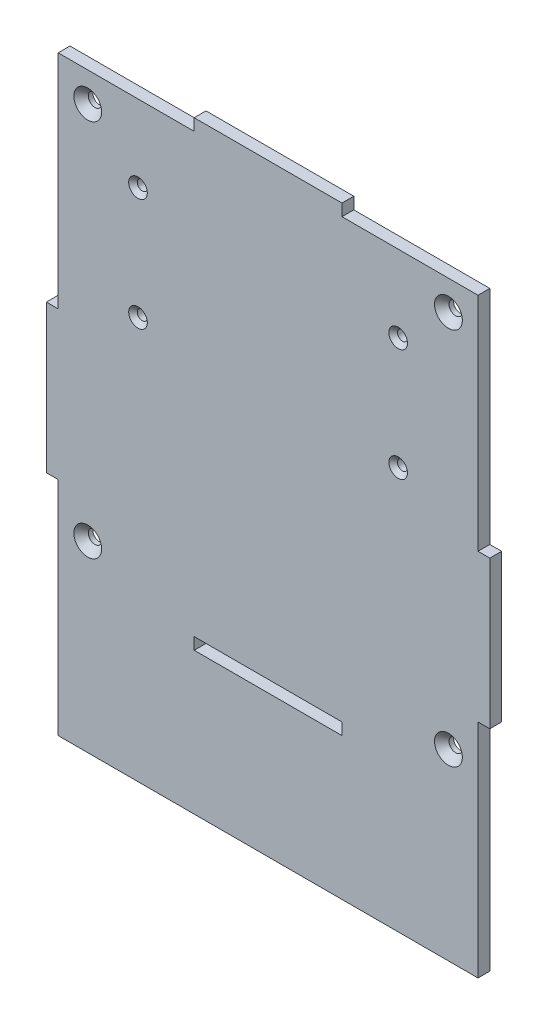
SolidWorks part; units mm, degrees
ref_plane "Front Plane" through (0, 0, 0) normal (0, 0, 1) x (1, 0, 0)
ref_plane "Top Plane" through (0, 0, 0) normal (0, 1, 0) x (1, 0, 0)
ref_plane "Right Plane" through (0, 0, 0) normal (1, 0, 0) x (0, 0, -1)
sketch "Sketch1" plane through (0, 0, 0) normal (0, 0, 1) x (1, 0, 0)
  line L0 (0, 104) -> (0, 0) construction
  line L1 (-71, -100) -> (71, -100)
  line L2 (-71, -100) -> (-71, 100)
  line L3 (-71, 100) -> (71, 100)
  line L4 (71, -100) -> (71, 100)
  line L5 (-71, -100) -> (71, 100) construction
  line L6 (-71, 100) -> (71, -100) construction
  line L7 (-71, 25) -> (-75, 25)
  line L8 (-71, 25) -> (-71, -25)
  line L9 (-71, -25) -> (-75, -25)
  line L10 (-75, 25) -> (-75, -25)
  line L11 (-25, 100) -> (25, 100)
  line L12 (-25, 100) -> (-25, 104)
  line L13 (-25, 104) -> (25, 104)
  line L14 (25, 100) -> (25, 104)
  line L15 (0, 0) -> (-75, 0) construction
  line L24 (71, -25) -> (75, -25)
  line L25 (75, 25) -> (75, -25)
  line L26 (71, 25) -> (75, 25)
  line L27 (71, 25) -> (71, -25)
  point P0 (0, 0)
  dimension "D1" = 142
  dimension "D2" = 200
  dimension "D3" = 4
  dimension "D4" = 4
  dimension "D5" = 50
  dimension "D6" = 50
extrude "Boss-Extrude2" add sketch "Sketch1" along normal blind 4
sketch "Sketch2" plane through (0, 0, 4) normal (0, 0, 1) x (1, 0, 0)
  line L0 (0, 0) -> (0, -50)
  line L1 (-25, -52) -> (25, -52)
  line L2 (-25, -52) -> (-25, -48)
  line L3 (-25, -48) -> (25, -48)
  line L4 (25, -52) -> (25, -48)
  line L5 (-25, -52) -> (25, -48) construction
  line L6 (-25, -48) -> (25, -52) construction
  point P0 (0, -50)
  dimension "D1" = 50
  dimension "D2" = 50
  dimension "D3" = 4
extrude "Cut-Extrude1" cut sketch "Sketch2" against normal up to next contours L3 L4 L1 L2
sketch "Sketch3" plane through (0, 0, 4) normal (0, 0, 1) x (1, 0, 0)
  line L0 (0, 55) -> (0, 0)
  line L1 (-44, 36) -> (44, 36)
  line L2 (-44, 36) -> (-44, 74)
  line L3 (-44, 74) -> (44, 74)
  line L4 (44, 36) -> (44, 74)
  line L5 (-44, 36) -> (44, 74) construction
  line L6 (-44, 74) -> (44, 36) construction
  point P0 (0, 55)
  dimension "D1" = 88
  dimension "D2" = 38
  dimension "D3" = 55
hole_wizard "CSK for M3 Countersunk Flat Head Screw1" positions "3DSketch1" profile "Sketch4" countersink size "M3" standard "ISO" end condition up to next
sketch3d "3DSketch1"
  point P0 (-44, 74, 4)
  point P3 (44, 74, 4)
  point P6 (44, 36, 4)
  point P9 (-44, 36, 4)
sketch "Sketch4" plane through (-44, 74, 4) normal (1, 0, 0) x (0, -1, 0)
  line L0 (0, 0) -> (0, 4)
  line L1 (0, 4) -> (1.7, 4)
  line L2 (1.7, 4) -> (1.7, 1.45)
  line L3 (1.7, 1.45) -> (3.15, 0)
  line L5 (3.15, 0) -> (0, 0)
  line L6 (-1.7, 1.45) -> (-3.15, 0) construction
  line L11 (0, -6.35) -> (0, 107.95) construction
  dimension "Thru Hole Dia." = 3.4
  dimension "Thru Hole Depth" = 4
  dimension "Near C'Sink Dia." = 6.3
  dimension "Near C'Sink Angle" = 90
sketch "Sketch5" plane through (0, 0, 4) normal (0, 0, 1) x (1, 0, 0)
  line L0 (-25, -48) -> (25, -48) construction
  line L1 (-61, 90) -> (61, 90)
  line L2 (-61, 90) -> (-61, -38)
  line L3 (-61, -38) -> (61, -38)
  line L4 (61, 90) -> (61, -38)
  line L5 (25, 100) -> (71, 100) construction
  line L6 (71, 25) -> (71, 100) construction
  line L7 (-71, 25) -> (-71, 100) construction
  dimension "D1" = 10
  dimension "D2" = 10
  dimension "D3" = 10
  dimension "D4" = 10
hole_wizard "CSK for M4 Countersunk Flat Head Screw1" positions "3DSketch2" profile "Sketch6" countersink size "M4" standard "ISO" end condition up to next
sketch3d "3DSketch2"
  point P0 (-61, 90, 4)
  point P3 (61, 90, 4)
  point P6 (61, -38, 4)
  point P9 (-61, -38, 4)
sketch "Sketch6" plane through (-61, 90, 4) normal (1, 0, 0) x (0, -1, 0)
  line L0 (0, 0) -> (0, 4)
  line L1 (0, 4) -> (2.25, 4)
  line L2 (2.25, 4) -> (2.25, 2.45)
  line L3 (2.25, 2.45) -> (4.7, 0)
  line L5 (4.7, 0) -> (0, 0)
  line L6 (-2.25, 2.45) -> (-4.7, 0) construction
  line L11 (0, -6.35) -> (0, 107.95) construction
  dimension "Thru Hole Dia." = 4.5
  dimension "Thru Hole Depth" = 4
  dimension "Near C'Sink Dia." = 9.4
  dimension "Near C'Sink Angle" = 90
